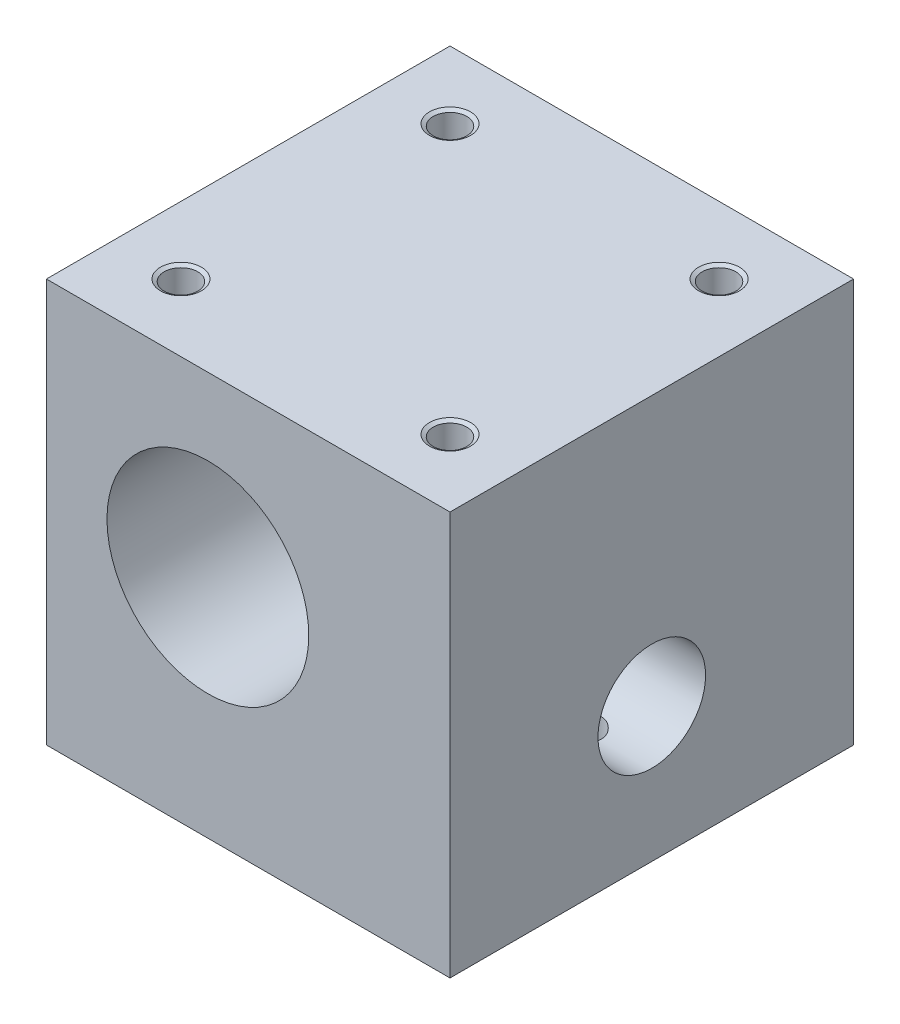
SolidWorks part; units mm, degrees
material "Lega 1060"
ref_plane "Piano frontale" through (0, 0, 0) normal (0, 0, 1) x (1, 0, 0)
ref_plane "Piano superiore" through (0, 0, 0) normal (0, 1, 0) x (1, 0, 0)
ref_plane "Piano destro" through (0, 0, 0) normal (1, 0, 0) x (0, 0, -1)
sketch "Schizzo1" plane through (0, 0, 0) normal (0, 0, 1) x (1, 0, 0)
  line L0 (12, 6.5764) -> (12, 28.444) construction
  line L1 (0, 0) -> (30, 0)
  line L2 (0, 0) -> (0, 30)
  line L3 (0, 30) -> (30, 30)
  line L4 (30, 0) -> (30, 30)
  line L5 (6.315, 16.8) -> (24.6155, 16.8) construction
  circle A0 centre (12, 16.8) radius 7.5
  dimension "D3" = 15
  dimension "D1" = 30
  dimension "D2" = 30
  dimension "D4" = 12
  dimension "D5" = 13.2
extrude "Estrusione-Estrusione1" add sketch "Schizzo1" along normal blind 30
sketch "Schizzo3" plane through (30, 0, 0) normal (1, 0, 0) x (0, 0, -1)
  line L2 (-15, 10.16) -> (-15, 24.3684) construction
  line L3 (-30, 0) -> (-30, 30) construction
  line L4 (0, 0) -> (0, 30) construction
  line L5 (-30, 0) -> (0, 0) construction
  point P0 (-15, 10)
  dimension "D1" = 10
hole_wizard "Foro Ø8.0 (8)-1" positions "Schizzo5" profile "Schizzo4" hole size "Ø8.0" standard "ISO"
sketch "Schizzo5" plane through (30, 0, 0) normal (1, 0, 0) x (0, 0, -1)
  point P0 (-15, 10)
sketch "Schizzo4" plane through (30, 10, 15) normal (0, 1, 0) x (0, 0, -1)
  line L0 (0, 0) -> (0, 12.4034)
  line L1 (0, 12.4034) -> (4, 10)
  line L2 (4, 10) -> (4, 0)
  line L5 (4, 0) -> (0, 0)
  line L10 (0, 12.4034) -> (-4, 10) construction
  line L11 (0, -6.35) -> (0, 107.95) construction
  dimension "Hole Dia." = 8
  dimension "Hole Depth" = 10
  dimension "Drill Angle" = 118
sketch "Schizzo6" plane through (0, 30, 0) normal (0, 1, 0) x (1, 0, 0)
  line L0 (-7.6843, -25) -> (41.504, -25) construction
  line L1 (0, -30) -> (0, 0) construction
  line L2 (30, -30) -> (0, -30) construction
  point P0 (5, -25)
  point P1 (25, -25)
  dimension "D1" = 20
  dimension "D2" = 5
  dimension "D3" = 5
hole_wizard "Foro filettato M3-1" positions "Schizzo8" profile "Schizzo7" tap size "M3" standard "ISO"
sketch "Schizzo8" plane through (0, 30, 0) normal (0, 1, 0) x (1, 0, 0)
  point P0 (5, -25)
  point P3 (25, -25)
sketch "Schizzo7" plane through (5, 30, 25) normal (1, 0, 0) x (0, 0, 1)
  line L0 (0, 0) -> (0, 9.2511)
  line L1 (0, 9.2511) -> (1.25, 8.5)
  line L2 (1.25, 8.5) -> (1.25, 0.1588)
  line L3 (1.25, 0.1588) -> (1.525, 0)
  line L5 (1.525, 0) -> (0, 0)
  line L6 (-1.25, 0.1588) -> (-1.525, 0) construction
  line L10 (0, 9.2511) -> (-1.25, 8.5) construction
  line L11 (0, -6.35) -> (0, 107.95) construction
  dimension "Tap Drill Dia." = 2.5
  dimension "Tap Drill Depth" = 8.5
  dimension "Near C'Sink Dia." = 3.05
  dimension "Near C'Sink Angle" = 120
  dimension "Drill Angle" = 118
cosmetic thread "Filettatura del foro1" parameters "D1"=6, "D2"=3
cosmetic thread "Filettatura del foro2" parameters "D1"=6, "D2"=3
ref_plane "Piano1" through (0, 0, 15) normal (0, 0, 1) x (1, 0, 0)
mirror "Specchia1" about plane through (0, 0, 15) normal (0, 0, 1) of "Foro filettato M3-1"
hole_wizard "Foro filettato M3-2" positions "Schizzo10" profile "Schizzo11" tap size "M3" standard "ISO"
sketch "Schizzo10" plane through (0, 0, 0) normal (0, -1, 0) x (-1, 0, 0)
  line L0 (0, 0) -> (-30, 0) construction
  line L1 (-30, -30) -> (-30, 0) construction
  point P0 (-25, -15)
  dimension "D1" = 15
  dimension "D2" = 5
sketch "Schizzo11" plane through (25, 0, 15) normal (1, 0, 0) x (0, 0, -1)
  line L0 (0, 0) -> (0, 9.2511)
  line L1 (0, 9.2511) -> (1.25, 8.5)
  line L2 (1.25, 8.5) -> (1.25, 0.1588)
  line L3 (1.25, 0.1588) -> (1.525, 0)
  line L5 (1.525, 0) -> (0, 0)
  line L6 (-1.25, 0.1588) -> (-1.525, 0) construction
  line L10 (0, 9.2511) -> (-1.25, 8.5) construction
  line L11 (0, -6.35) -> (0, 107.95) construction
  dimension "Tap Drill Dia." = 2.5
  dimension "Tap Drill Depth" = 8.5
  dimension "Near C'Sink Dia." = 3.05
  dimension "Near C'Sink Angle" = 120
  dimension "Drill Angle" = 118
sketch "Schizzo12" plane through (0, -325.5594, 0) normal (0, 1, 0) x (1, 0, 0)
  line L0 (46.5896, 4) -> (357.1852, 4) construction
